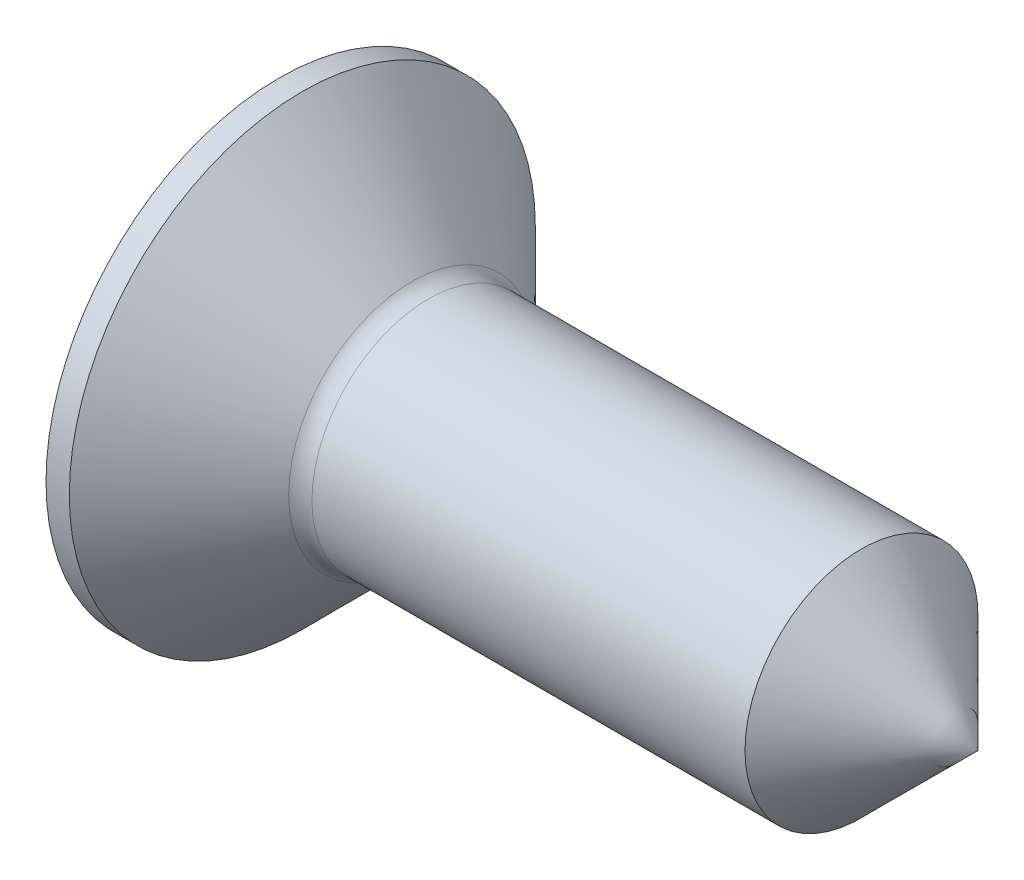
SolidWorks part; units mm, degrees
ref_plane "Front" through (0, 0, 0) normal (0, 0, 1) x (1, 0, 0)
ref_plane "Top" through (0, 0, 0) normal (0, 1, 0) x (1, 0, 0)
ref_plane "Right" through (0, 0, 0) normal (1, 0, 0) x (0, 0, -1)
sketch "Sketch1" plane through (0, 0, 0) normal (0, 1, 0) x (1, 0, 0)
  line L0 (-7.2405, 0) -> (8.2353, 0) construction
  line L1 (1.8, 1) -> (6.6, 1)
  line L2 (1.8, 1) -> (0.8, 2)
  line L3 (6.6, 1) -> (6.6, 0)
  line L4 (0.8, 2) -> (0.6, 2)
  line L5 (6.6, 0) -> (0, 0)
  arc A0 (0.6, 2) -> (0, 0) centre (3.6333, 0) ccw
  dimension "D1" = 45
  dimension "k" = 1.2
  dimension "l" = 6
revolve "Base" add sketch "Sketch1" angle 360 about L0
cosmetic thread "ThreadCosmetic1" [suppressed] parameters "D1"=3, "D2"=1.5
fillet "Fillet1" radius 0.2 1 edges at (1.8, 0, 1)
sketch "Sketch4" plane through (0, 0, 0) normal (0, 0, 1) x (1, 0, 0)
  line L0 (4.6467, 0) -> (7.1195, 0) construction
  line L2 (7.21, 0) -> (7.21, 20)
  line L3 (7.21, 20) -> (-13.4, 20)
  line L4 (-13.4, 20) -> (6.6, 0)
  line L5 (6.6, 0) -> (7.21, 0)
  line L6 (6.6, -1) -> (6.6, 1) construction
  dimension "D1" = 45
  dimension "D2" = 20
  dimension "D3" = 0.61
revolve "Cut-Revolve1" cut sketch "Sketch4" angle 360 about L0
sketch "Sketch3" plane through (0, 0, 0) normal (1, 0, 0) x (0, 0, -1)
  line L0 (2.315, 0) -> (-2.7642, 0) construction
  line L2 (0, 2.5823) -> (0, -2.9096) construction
  line L3 (-0.3375, 0.3375) -> (-1.35, 0.3375)
  line L4 (0.3375, -1.35) -> (-0.3375, -1.35)
  line L5 (0.3375, -1.35) -> (0.3375, -0.3375)
  line L6 (0.3375, 1.35) -> (-0.3375, 1.35)
  line L7 (-0.3375, -1.35) -> (-0.3375, -0.3375)
  line L8 (1.35, 0.3375) -> (0.3375, 0.3375)
  line L9 (1.35, 0.3375) -> (1.35, -0.3375)
  line L10 (1.35, -0.3375) -> (0.3375, -0.3375)
  line L11 (-1.35, 0.3375) -> (-1.35, -0.3375)
  line L12 (-0.3375, -0.3375) -> (-1.35, -0.3375)
  line L13 (-0.3375, 0.3375) -> (-0.3375, 1.35)
  line L14 (0.3375, 0.3375) -> (0.3375, 1.35)
  point P4 (-0.3375, 0.3375)
  point P26 (0.3375, 0.3375)
  dimension "D2" = 2.7
  dimension "D3" = 0.675
  dimension "D4" = 0.675
ref_plane "Plane1" through (1.65, 0, 0) normal (1, 0, 0) x (0, 0, -1)
sketch "Sketch6" plane through (1.65, 0, 0) normal (1, 0, 0) x (0, 0, -1)
  point P0 (0, 0)
loft "Cut-Loft1" cut profiles "Sketch3", "Sketch6"
sketch "Sketch7" plane through (0, 0, 0) normal (0, 0, 1) x (1, 0, 0)
  line L0 (2.6, 1.2) -> (2.85, 1.2)
  line L1 (2.85, 1.2) -> (2.85, 1)
  line L2 (2.85, 1) -> (2.725, 0.7835)
  line L3 (2.6, 1) -> (2.725, 0.7835)
  line L4 (2.6, 1.2) -> (2.6, 1)
  line L5 (10.7743, 0) -> (0, 0) construction
  line L6 (2.6, 1) -> (2.85, 1) construction
  line L7 (2.725, 1) -> (2.725, 0.7835) construction
  line L8 (5.6, 1) -> (1.8828, 1) construction
  point P5 (2.725, 1.2)
  dimension "D2" = 0.25
  dimension "D3" = 4
revolve "Cut-Revolve10" [suppressed] cut sketch "Sketch7" angle 360 about L5
pattern_linear "LPattern10" [suppressed] count 8 spacing 0.5 along (1, 0, 0) of bodies 105
equation "\"D4@Sketch3\" = \"m@Sketch3\" / 4"
equation "\"D2@Sketch3\" = \"m@Sketch3\""
equation "\"D3@Sketch3\" = \"m@Sketch3\" / 4"
equation "\"D1@Plane1\" = \"k@Sketch1\" + \"f@Sketch1\"  -  0.15"
equation "\"D2@Sketch7\" = (  \"d@Sketch1\" - \"D2@ThreadCosmetic1\" )  / 2"
equation "\"D3@Sketch7\" = \"D1@ThreadCosmetic1\" + \"d@Sketch1\" / 2"
equation "\"D3@LPattern10\" = \"D2@Sketch7\" *2"
equation "\"D1@LPattern10\" = \"D3@Sketch7\" / \"D3@LPattern10\""
